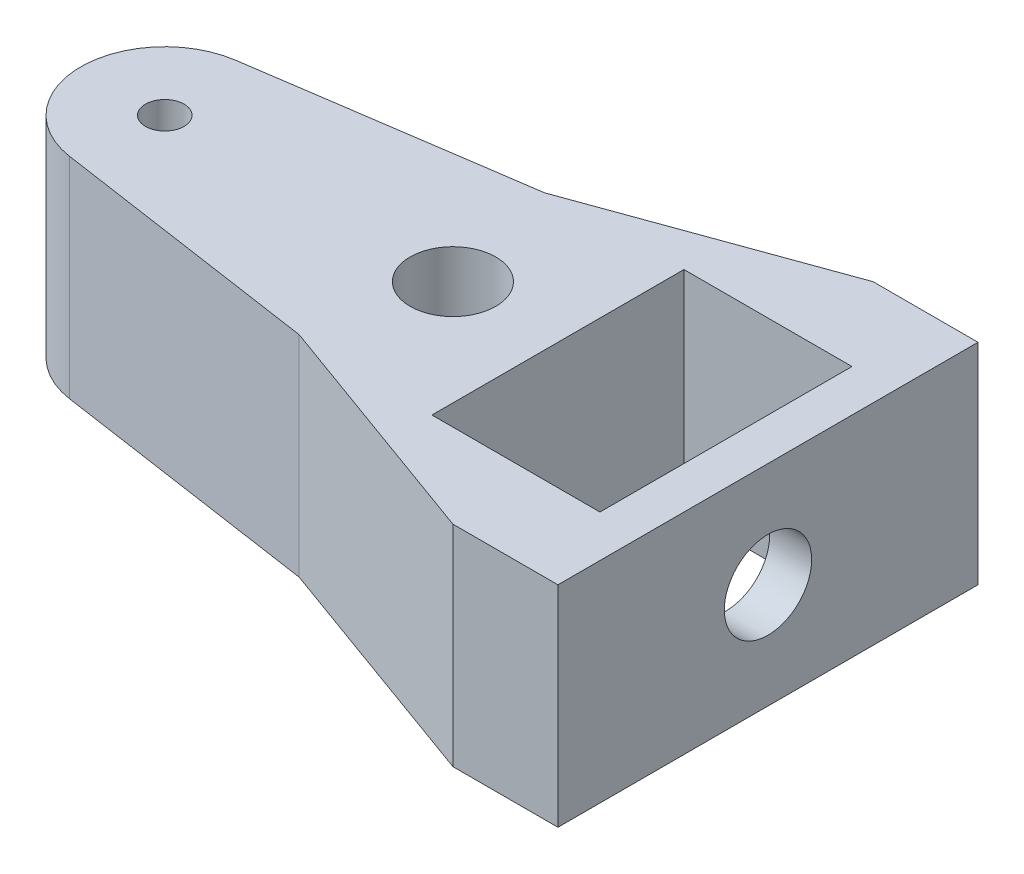
SolidWorks part; units mm, degrees
ref_plane "Front Plane" through (0, 0, 0) normal (0, 0, 1) x (1, 0, 0)
ref_plane "Top Plane" through (0, 0, 0) normal (0, 1, 0) x (1, 0, 0)
ref_plane "Right Plane" through (0, 0, 0) normal (1, 0, 0) x (0, 0, -1)
sketch "Sketch1" plane through (0, 0, 0) normal (0, 1, 0) x (1, 0, 0)
  line L4 (37.5, 12.5) -> (37.5, -12.5)
  line L5 (37.5, 12.5) -> (37.5, 25)
  line L6 (37.5, 25) -> (25, 25)
  line L12 (25, -25) -> (37.5, -25)
  line L14 (37.5, -25) -> (37.5, -12.5)
  line L16 (-3.6827, 14.6193) -> (25, 25)
  line L17 (-35.7577, 9.8932) -> (-3.6827, 14.6193)
  line L18 (-35.7577, -9.8932) -> (-3.6827, -14.6193)
  line L19 (32.5, 15) -> (12.5, 15)
  line L20 (32.5, 15) -> (32.5, -15)
  line L21 (32.5, -15) -> (12.5, -15)
  line L22 (12.5, 15) -> (12.5, -15)
  line L23 (22.5, -15) -> (22.5, 15) construction
  line L24 (32.5, 0) -> (12.5, 0) construction
  line L26 (25, -25) -> (-3.6827, -14.6193)
  circle A0 centre (0, 0) radius 5.1
  circle A1 centre (-34.3, 0) radius 2.3
  arc A2 (-35.7577, 9.8932) -> (-35.7577, -9.8932) centre (-34.3, 0) ccw
  circle A5 centre (0, 0) radius 15 construction
  point P0 (0, 0)
  point P25 (0, 0)
  point P26 (0, 0)
  point P655 (22.5, 0)
  dimension "D3" = 10.2
  dimension "D4" = 34.3
  dimension "D5" = 4.6
  dimension "D6" = 20
  dimension "D1" = 37.5
  dimension "D10" = 30
  dimension "D2" = 25
  dimension "D7" = 12.5
  dimension "D8" = 25
  dimension "D9" = 25
  dimension "D11" = 5
  dimension "D12" = 10
  dimension "D13" = 10
  dimension "D14" = 20
extrude "Boss-Extrude1" add sketch "Sketch1" along normal blind 25
sketch "Sketch2" plane through (37.5, 0, 0) normal (1, 0, 0) x (0, 0, -1)
  line L0 (12.5, 25) -> (12.5, 0) construction
  line L1 (-25, 25) -> (25, 25) construction
  circle A0 centre (0, 12.5) radius 5.2
  dimension "D1" = 10.4
  dimension "D2" = 12.5
  dimension "D3" = 12.5
extrude "Cut-Extrude2" cut sketch "Sketch2" against normal blind 20
